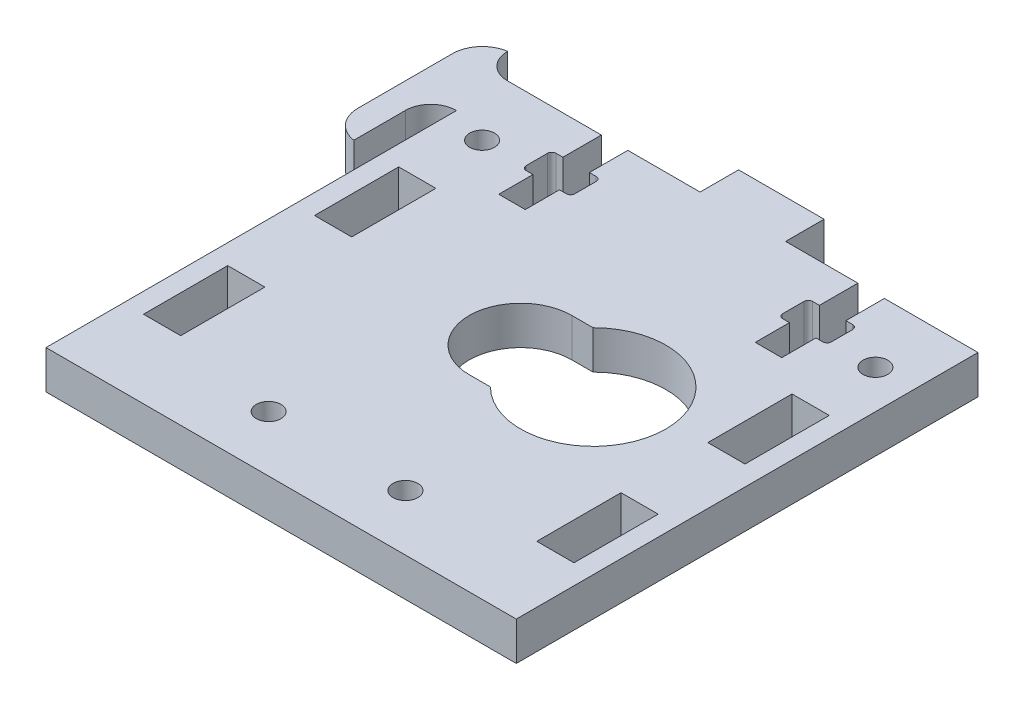
SolidWorks part; units mm, degrees
ref_plane "Front Plane" through (0, 0, 0) normal (0, 0, 1) x (1, 0, 0)
ref_plane "Top Plane" through (0, 0, 0) normal (0, 1, 0) x (1, 0, 0)
ref_plane "Right Plane" through (0, 0, 0) normal (1, 0, 0) x (0, 0, -1)
sketch "Sketch1" plane through (0, 0, 0) normal (0, 1, 0) x (1, 0, 0)
  line L1 (-27.5, 27) -> (27.5, 27)
  line L2 (-27.5, 27) -> (-27.5, -27)
  line L3 (-27.5, -27) -> (27.5, -27)
  line L4 (27.5, 27) -> (27.5, -27)
  line L5 (-27.5, 27) -> (27.5, -27) construction
  line L6 (-27.5, -27) -> (27.5, 27) construction
  point P0 (0, 0)
  dimension "D1" = 55
  dimension "D2" = 54
extrude "MainShape" add sketch "Sketch1" along normal blind 4.5
sketch "Sketch2" plane through (0, 4.5, 0) normal (0, 1, 0) x (1, 0, 0)
  line L0 (0, -27) -> (0, 27) construction
  line L1 (-27.5, -27) -> (27.5, -27) construction
  line L2 (27.5, 27) -> (-27.5, 27) construction
  line L4 (-5, 31.5) -> (5, 31.5)
  line L5 (-5, 31.5) -> (-5, 22.5)
  line L6 (-5, 22.5) -> (5, 22.5)
  line L7 (5, 31.5) -> (5, 22.5)
  line L8 (-5, 31.5) -> (5, 22.5) construction
  line L9 (-5, 22.5) -> (5, 31.5) construction
  dimension "D1" = 10
  dimension "D2" = 4.5
extrude "Tab1" add sketch "Sketch2" against normal through all
sketch "Sketch4" plane through (0, 4.5, 0) normal (0, 1, 0) x (1, 0, 0)
  line L0 (0, 31.5) -> (0, -27) construction
  line L1 (5, 31.5) -> (-5, 31.5) construction
  line L2 (-27.5, -27) -> (27.5, -27) construction
  line L3 (-15, 27) -> (-15, 15) construction
  line L4 (-5, 27) -> (-27.5, 27) construction
  line L5 (-13.45, 15) -> (-16.55, 15) construction
  line L6 (-16.55, 15) -> (-16.55, 27) construction
  line L7 (-13.45, 15) -> (-16.55, 15)
  line L8 (-16.55, 15) -> (-16.55, 19)
  line L9 (-16.55, 19) -> (-17.35, 19)
  line L10 (-17.85, 19.5) -> (-17.85, 22)
  line L11 (-17.35, 22.5) -> (-16.55, 22.5)
  line L12 (-16.55, 22.5) -> (-16.55, 27)
  line L13 (-16.55, 27) -> (-13.45, 27)
  line L14 (-13.45, 15) -> (-13.45, 27) construction
  line L15 (-13.45, 22.5) -> (-13.45, 27)
  line L16 (-12.65, 22.5) -> (-13.45, 22.5)
  line L17 (-12.15, 19.5) -> (-12.15, 22)
  line L18 (-13.45, 19) -> (-12.65, 19)
  line L19 (-13.45, 15) -> (-13.45, 19)
  line L20 (13.45, 15) -> (13.45, 27) construction
  line L21 (16.55, 15) -> (16.55, 27) construction
  line L22 (13.45, 15) -> (16.55, 15) construction
  line L23 (15, 27) -> (15, 15) construction
  line L24 (13.45, 15) -> (13.45, 19)
  line L25 (13.45, 19) -> (12.65, 19)
  line L26 (12.15, 19.5) -> (12.15, 22)
  line L27 (12.65, 22.5) -> (13.45, 22.5)
  line L28 (13.45, 22.5) -> (13.45, 27)
  line L29 (16.55, 27) -> (13.45, 27)
  line L30 (16.55, 22.5) -> (16.55, 27)
  line L31 (17.35, 22.5) -> (16.55, 22.5)
  line L32 (17.85, 19.5) -> (17.85, 22)
  line L33 (16.55, 19) -> (17.35, 19)
  line L34 (16.55, 15) -> (16.55, 19)
  line L35 (13.45, 15) -> (16.55, 15)
  arc A0 (-17.35, 19) -> (-17.85, 19.5) centre (-17.35, 19.5) cw
  arc A1 (-12.15, 19.5) -> (-12.65, 19) centre (-12.65, 19.5) cw
  arc A2 (-12.65, 22.5) -> (-12.15, 22) centre (-12.65, 22) cw
  arc A3 (-17.85, 22) -> (-17.35, 22.5) centre (-17.35, 22) cw
  arc A4 (17.85, 22) -> (17.35, 22.5) centre (17.35, 22) ccw
  arc A5 (12.65, 22.5) -> (12.15, 22) centre (12.65, 22) ccw
  arc A6 (12.15, 19.5) -> (12.65, 19) centre (12.65, 19.5) ccw
  arc A7 (17.35, 19) -> (17.85, 19.5) centre (17.35, 19.5) ccw
  point P24 (-17.85, 19)
  point P27 (-12.15, 19)
  point P30 (-12.15, 22.5)
  point P33 (-17.85, 22.5)
  point P56 (17.85, 22.5)
  point P57 (12.15, 22.5)
  point P58 (12.15, 19)
  point P59 (17.85, 19)
  dimension "D7" = 0.5
  dimension "D1" = 12
  dimension "D2" = 1.55
  dimension "D3" = 3.5
  dimension "D4" = 2.85
  dimension "D5" = 8
  dimension "D6" = 15
extrude "Cut-Extrude2" cut sketch "Sketch4" against normal through all
sketch "Sketch5" plane through (0, 4.5, 0) normal (0, 1, 0) x (1, 0, 0)
  line L0 (0, -27) -> (0, 31.5) construction
  line L1 (-27.5, -27) -> (27.5, -27) construction
  line L2 (5, 31.5) -> (-5, 31.5) construction
  line L3 (23, 27) -> (23, -27) construction
  line L4 (27.5, 27) -> (16.55, 27) construction
  line L5 (-23, 27) -> (-23, -27) construction
  line L6 (20.825, 11.925) -> (25.175, 11.925)
  line L7 (20.825, 11.925) -> (20.825, 2.075)
  line L8 (20.825, 2.075) -> (25.175, 2.075)
  line L9 (25.175, 11.925) -> (25.175, 2.075)
  line L10 (20.825, 11.925) -> (25.175, 2.075) construction
  line L11 (20.825, 2.075) -> (25.175, 11.925) construction
  line L12 (-20.825, 2.075) -> (-25.175, 11.925) construction
  line L13 (-20.825, 11.925) -> (-25.175, 2.075) construction
  line L14 (-25.175, 11.925) -> (-25.175, 2.075)
  line L15 (-20.825, 2.075) -> (-25.175, 2.075)
  line L16 (-20.825, 11.925) -> (-20.825, 2.075)
  line L17 (-20.825, 11.925) -> (-25.175, 11.925)
  line L18 (-27.5, -3) -> (27.5, -3) construction
  line L19 (-27.5, 27) -> (-27.5, -27) construction
  line L20 (27.5, -27) -> (27.5, 27) construction
  line L21 (-20.825, -17.925) -> (-25.175, -8.075) construction
  line L22 (-20.825, -8.075) -> (-25.175, -17.925) construction
  line L23 (20.825, -8.075) -> (25.175, -17.925) construction
  line L24 (20.825, -17.925) -> (25.175, -8.075) construction
  line L25 (-20.825, -17.925) -> (-25.175, -17.925)
  line L26 (-20.825, -17.925) -> (-20.825, -8.075)
  line L27 (-20.825, -8.075) -> (-25.175, -8.075)
  line L28 (-25.175, -17.925) -> (-25.175, -8.075)
  line L29 (25.175, -17.925) -> (25.175, -8.075)
  line L30 (20.825, -8.075) -> (25.175, -8.075)
  line L31 (20.825, -17.925) -> (20.825, -8.075)
  line L32 (20.825, -17.925) -> (25.175, -17.925)
  line L33 (-20.825, 11.925) -> (-25.175, 2.075) construction
  point P10 (23, 7)
  point P21 (-23, 7)
  point P36 (-23, -13)
  point P37 (23, -13)
  dimension "D1" = 23
  dimension "D2" = 9.85
  dimension "D3" = 4.35
  dimension "D4" = 20
  dimension "D5" = 20
extrude "Cut-Extrude3" cut sketch "Sketch5" against normal through all
sketch "Sketch6" plane through (0, 4.5, 0) normal (0, 1, 0) x (1, 0, 0)
  line L0 (0, -27) -> (0, 27) construction
  line L1 (5, 31.5) -> (-5, 31.5) construction
  line L3 (-27.5, 1) -> (27.5, 1) construction
  line L4 (-27.5, 27) -> (-27.5, -27) construction
  line L5 (27.5, -27) -> (27.5, 27) construction
  line L6 (27.5, 27) -> (16.55, 27) construction
  line L7 (-27.5, -27) -> (27.5, -27) construction
  line L9 (-27.5, 27) -> (27.5, 27) construction
  circle A0 centre (0, 1) radius 12
  point P4 (0, 31.5)
  dimension "D1" = 24
  dimension "D2" = 26
extrude "Cut-Extrude4" cut sketch "Sketch6" against normal through all
sketch "Sketch7" plane through (0, 4.5, 0) normal (0, 1, 0) x (1, 0, 0)
  line L0 (0, 1) -> (0, -27) construction
  line L3 (-27.5, -27) -> (27.5, -27) construction
  line L4 (8, -20.46) -> (-8, -20.46) construction
  circle A1 centre (-8, -20.46) radius 1.45
  circle A2 centre (8, -20.46) radius 1.45
  point P8 (0, -20.46)
  dimension "D1" = 2.9
  dimension "D3" = 21.46
extrude "Cut-Extrude5" [suppressed] cut sketch "Sketch7" against normal through all
sketch "Sketch8" plane through (0, 4.5, 0) normal (0, 1, 0) x (1, 0, 0)
  line L0 (-12, 1) -> (12, 1) construction
  line L1 (0, 1) -> (0, -20.46) construction
  line L2 (8, -20.46) -> (-8, -20.46) construction
  line L3 (0, -11) -> (0, 13) construction
  circle A0 centre (-8, -20.46) radius 1.45
  circle A1 centre (0, 1) radius 12 construction
  circle A2 centre (8, -20.46) radius 1.45
  dimension "D3" = 2.9
  dimension "D1" = 90
  dimension "D4" = 21.46
extrude "Cut-Extrude6" cut sketch "Sketch8" against normal through all
sketch "Sketch9" plane through (0, 4.5, 0) normal (0, 1, 0) x (1, 0, 0)
  line L0 (0, -27) -> (0, 31.5) construction
  line L1 (-27.5, -27) -> (27.5, -27) construction
  line L2 (5, 31.5) -> (-5, 31.5) construction
  line L3 (16, -27) -> (16, -16) construction
  line L4 (14.45, -16) -> (17.55, -16) construction
  line L5 (17.55, -16) -> (17.55, -27) construction
  line L6 (17.55, -27) -> (17.55, -22.5)
  line L7 (17.55, -22.5) -> (18.35, -22.5)
  line L8 (18.85, -22) -> (18.85, -19.5)
  line L9 (18.35, -19) -> (17.55, -19)
  line L10 (17.55, -19) -> (17.55, -16)
  line L11 (17.55, -16) -> (14.45, -16)
  line L12 (17.55, -27) -> (14.45, -27)
  line L13 (14.45, -16) -> (14.45, -27) construction
  line L14 (14.45, -19) -> (14.45, -16)
  line L15 (13.65, -19) -> (14.45, -19)
  line L16 (13.15, -22) -> (13.15, -19.5)
  line L17 (14.45, -22.5) -> (13.65, -22.5)
  line L18 (14.45, -27) -> (14.45, -22.5)
  line L19 (-14.45, -16) -> (-14.45, -27) construction
  line L20 (-17.55, -16) -> (-17.55, -27) construction
  line L21 (-14.45, -16) -> (-17.55, -16) construction
  line L22 (-16, -27) -> (-16, -16) construction
  line L23 (-14.45, -27) -> (-14.45, -22.5)
  line L24 (-14.45, -22.5) -> (-13.65, -22.5)
  line L25 (-13.15, -22) -> (-13.15, -19.5)
  line L26 (-13.65, -19) -> (-14.45, -19)
  line L27 (-14.45, -19) -> (-14.45, -16)
  line L28 (-17.55, -27) -> (-14.45, -27)
  line L29 (-17.55, -16) -> (-14.45, -16)
  line L30 (-17.55, -19) -> (-17.55, -16)
  line L31 (-18.35, -19) -> (-17.55, -19)
  line L32 (-18.85, -22) -> (-18.85, -19.5)
  line L33 (-17.55, -22.5) -> (-18.35, -22.5)
  line L34 (-17.55, -27) -> (-17.55, -22.5)
  arc A0 (18.35, -22.5) -> (18.85, -22) centre (18.35, -22) ccw
  arc A1 (18.85, -19.5) -> (18.35, -19) centre (18.35, -19.5) ccw
  arc A2 (13.15, -19.5) -> (13.65, -19) centre (13.65, -19.5) cw
  arc A3 (13.65, -22.5) -> (13.15, -22) centre (13.65, -22) cw
  arc A4 (-13.65, -22.5) -> (-13.15, -22) centre (-13.65, -22) ccw
  arc A5 (-13.15, -19.5) -> (-13.65, -19) centre (-13.65, -19.5) ccw
  arc A6 (-18.85, -19.5) -> (-18.35, -19) centre (-18.35, -19.5) cw
  arc A7 (-18.35, -22.5) -> (-18.85, -22) centre (-18.35, -22) cw
  point P16 (18.85, -22.5)
  point P19 (18.85, -19)
  point P30 (13.15, -19)
  point P31 (13.15, -22.5)
  point P54 (-13.15, -22.5)
  point P55 (-13.15, -19)
  point P56 (-18.85, -19)
  point P57 (-18.85, -22.5)
  dimension "D7" = 0.5
  dimension "D2" = 1.55
  dimension "D1" = 11
  dimension "D3" = 8
  dimension "D4" = 3.5
  dimension "D5" = 2.85
  dimension "D6" = 16
extrude "Cut-Extrude7" [suppressed] cut sketch "Sketch9" against normal through all
sketch "Sketch10" [suppressed] plane through (0, 0, 27) normal (0, 0, 1) x (1, 0, 0)
  line L0 (-27.5, 2.25) -> (27.5, 2.25) construction
  line L1 (-27.5, 4.5) -> (-27.5, 0) construction
  line L2 (27.5, 4.5) -> (27.5, 0) construction
  line L3 (-16, 4.5) -> (-16, 0) construction
  line L4 (-14.25, 4.5) -> (-17.75, 4.5) construction
  line L5 (16, 4.5) -> (16, 0) construction
  line L6 (17.75, 4.5) -> (14.25, 4.5) construction
  line L7 (17.75, 0) -> (14.25, 0) construction
  line L8 (-14.25, 0) -> (-17.75, 0) construction
  circle A0 centre (-16, 2.25) radius 1.6
  circle A1 centre (16, 2.25) radius 1.6
  dimension "D1" = 3.2
  dimension "D2" = 3.2
sketch "Sketch11" plane through (0, 4.5, 0) normal (0, 1, 0) x (1, 0, 0)
  line L0 (-20.825, 7) -> (-25.175, 7) construction
  line L1 (-20.825, 2.075) -> (-20.825, 11.925) construction
  line L2 (-25.175, 11.925) -> (-25.175, 2.075) construction
  line L3 (-23, 7) -> (-23, 27) construction
  line L4 (-16.55, 27) -> (-27.5, 27) construction
  line L5 (0, 31.5) -> (0, 0) construction
  line L6 (5, 31.5) -> (-5, 31.5) construction
  line L7 (23, 7) -> (23, 27) construction
  line L8 (20.825, 7) -> (25.175, 7) construction
  line L9 (-23, 7) -> (-23, 27) construction
  circle A0 centre (-23, 19.5) radius 1.45
  circle A1 centre (23, 19.5) radius 1.45
  dimension "D1" = 2.9
  dimension "D2" = 7.5
extrude "Cut-Extrude8" cut sketch "Sketch11" against normal through all
sketch "Sketch12" [suppressed] plane through (0, 4.5, 0) normal (0, 1, 0) x (1, 0, 0)
  line L0 (-27.5, -7) -> (-34, -17)
  line L1 (-27.5, 27) -> (-27.5, -27) construction
  line L2 (-34, -17) -> (-34, -27)
  line L3 (-34, -27) -> (-27.5, -27)
  line L4 (-27.5, -27) -> (-27.5, -7)
  line L5 (-27.5, -27) -> (27.5, -27) construction
  line L6 (0, -27) -> (0, 31.5) construction
  line L7 (5, 31.5) -> (-5, 31.5) construction
  line L8 (27.5, -27) -> (27.5, -7)
  line L9 (34, -27) -> (27.5, -27)
  line L10 (34, -17) -> (34, -27)
  line L11 (27.5, -7) -> (34, -17)
  point P4 (0, -27)
  dimension "D1" = 34
  dimension "D2" = 10
  dimension "D3" = 20
extrude "Boss-Extrude1" [suppressed] add sketch "Sketch12" against normal through all
sketch "Sketch14" [suppressed] plane through (0, 4.5, 0) normal (0, 1, 0) x (1, 0, 0)
  line L0 (-34, -27) -> (34, -27) construction
  line L2 (-34, -27) -> (34, -27) construction
  line L3 (0, -27) -> (0, 31.5) construction
  line L4 (5, 31.5) -> (-5, 31.5) construction
  line L6 (26.25, -16.5) -> (26.25, -27) construction
  line L8 (-28, -27) -> (-28, -16.5) construction
  line L9 (-26.25, -16.5) -> (-29.75, -16.5) construction
  line L10 (-29.75, -16.5) -> (-29.75, -27) construction
  line L11 (-26.25, -27) -> (-29.75, -27)
  line L12 (-29.75, -27) -> (-29.75, -23.2)
  line L13 (-29.75, -23.2) -> (-30.75, -23.2)
  line L14 (-31, -22.95) -> (-31, -19.25)
  line L15 (-30.75, -19) -> (-29.75, -19)
  line L16 (-29.75, -19) -> (-29.75, -16.5)
  line L17 (-29.75, -16.5) -> (-26.25, -16.5)
  line L18 (-26.25, -16.5) -> (-26.25, -27) construction
  line L19 (-26.25, -19) -> (-26.25, -16.5)
  line L20 (-25.25, -19) -> (-26.25, -19)
  line L21 (-25, -22.95) -> (-25, -19.25)
  line L22 (-26.25, -23.2) -> (-25.25, -23.2)
  line L23 (-26.25, -27) -> (-26.25, -23.2)
  line L24 (29.75, -16.5) -> (29.75, -27) construction
  line L25 (26.25, -16.5) -> (29.75, -16.5) construction
  line L26 (28, -27) -> (28, -16.5) construction
  line L27 (26.25, -27) -> (26.25, -23.2)
  line L28 (26.25, -23.2) -> (25.25, -23.2)
  line L29 (25, -22.95) -> (25, -19.25)
  line L30 (25.25, -19) -> (26.25, -19)
  line L31 (26.25, -19) -> (26.25, -16.5)
  line L32 (29.75, -16.5) -> (26.25, -16.5)
  line L33 (29.75, -19) -> (29.75, -16.5)
  line L34 (30.75, -19) -> (29.75, -19)
  line L35 (31, -22.95) -> (31, -19.25)
  line L36 (29.75, -23.2) -> (30.75, -23.2)
  line L37 (29.75, -27) -> (29.75, -23.2)
  line L38 (26.25, -27) -> (29.75, -27)
  line L39 (-26.25, -16.5) -> (-26.25, -27) construction
  arc A0 (-30.75, -23.2) -> (-31, -22.95) centre (-30.75, -22.95) cw
  arc A1 (-31, -19.25) -> (-30.75, -19) centre (-30.75, -19.25) cw
  arc A2 (-25, -19.25) -> (-25.25, -19) centre (-25.25, -19.25) ccw
  arc A3 (-25.25, -23.2) -> (-25, -22.95) centre (-25.25, -22.95) ccw
  arc A4 (25.25, -23.2) -> (25, -22.95) centre (25.25, -22.95) cw
  arc A5 (25, -19.25) -> (25.25, -19) centre (25.25, -19.25) cw
  arc A6 (31, -19.25) -> (30.75, -19) centre (30.75, -19.25) ccw
  arc A7 (30.75, -23.2) -> (31, -22.95) centre (30.75, -22.95) ccw
  point P2 (0, -27)
  dimension "D10" = 0.5
  dimension "D4" = 1.55
  dimension "D6" = 11
  dimension "D2" = 28
  dimension "D3" = 2.85
  dimension "D5" = 3.5
  dimension "D7" = 8
extrude "Cut-Extrude9" [suppressed] cut sketch "Sketch14" against normal through all
sketch "Sketch15" plane through (0, 4.5, 0) normal (0, 1, 0) x (1, 0, 0)
  circle A0 centre (0, 1) radius 12
  circle A1 centre (0, 1) radius 6
  circle A2 centre (0, 1) radius 12 construction
  dimension "D1" = 12
extrude "Boss-Extrude2" add sketch "Sketch15" against normal through all
sketch "Sketch16" plane through (0, 4.5, 0) normal (0, 1, 0) x (1, 0, 0)
  line L0 (0, 1) -> (27.5, 1) construction
  line L1 (27.5, -27) -> (27.5, 27) construction
  line L2 (0, 7) -> (2.4792, 7)
  line L3 (0, -5) -> (2.4792, -5)
  line L4 (0, 7) -> (0, -5)
  arc A0 (2.4792, -5) -> (2.4792, 7) centre (8.5, 1) ccw
  circle A1 centre (0, 1) radius 6 construction
  dimension "D1" = 17
  dimension "D2" = 8.5
extrude "Cut-Extrude10" cut sketch "Sketch16" against normal through all
sketch "Sketch17" plane through (0, 4.5, 0) normal (0, 1, 0) x (1, 0, 0)
  line L0 (-27.5, 22) -> (-27.5, 18) construction
  line L1 (-27.5, 27) -> (-27.5, -27) construction
  line L2 (-27.5, 25.5) -> (-27.5, 23.5)
  line L3 (-29, 22) -> (-29, 18)
  line L4 (-27.5, 22) -> (-27.5, 18) construction
  line L5 (-27.5, 16.5) -> (-27.5, 14.5)
  line L6 (-31, 22) -> (-31, 18)
  line L7 (-27.5, 25.5) -> (-27.5, 14.5) construction
  arc A0 (-27.5, 23.5) -> (-29, 22) centre (-27.5, 22) ccw
  arc A1 (-29, 18) -> (-27.5, 16.5) centre (-27.5, 18) ccw
  arc A2 (-27.5, 25.5) -> (-31, 22) centre (-27.5, 22) ccw
  arc A3 (-31, 18) -> (-27.5, 14.5) centre (-27.5, 18) ccw
  point P10 (-27.5, 20)
  dimension "D1" = 1.5
  dimension "D2" = 1.5
  dimension "D3" = 2
  dimension "D4" = 4
  dimension "D5" = 20
  dimension "D7" = 2
extrude "CableTieSlot" [suppressed] add sketch "Sketch17" against normal through all
sketch "Sketch18" plane through (0, 4.5, 0) normal (0, 1, 0) x (1, 0, 0)
  line L0 (-27.5, 27) -> (-27.55, 27)
  line L1 (-33.5, 30) -> (-33.5, 12)
  line L2 (-33.5, 12) -> (-30.5, 12)
  line L3 (-30.5, 12) -> (-30.5, 18.05)
  line L4 (-27.55, 21) -> (-27.5, 21)
  line L5 (-27.5, 27) -> (-27.5, -27) construction
  line L6 (-27.5, 21) -> (-27.5, 27)
  line L7 (-16.55, 27) -> (-27.5, 27) construction
  line L8 (-33.5, 30) -> (-30.5, 30)
  line L9 (-30.5, 30) -> (-30.5, 29.95)
  arc A0 (-27.55, 27) -> (-30.5, 29.95) centre (-27.55, 29.95) cw
  arc A1 (-30.5, 18.05) -> (-27.55, 21) centre (-27.55, 18.05) cw
  point P17 (-30.5, 27)
  dimension "D1" = 2.95
  dimension "D2" = 2.95
  dimension "D3" = 6
  dimension "D4" = 3
  dimension "D5" = 15
  dimension "D6" = 3
  dimension "D7" = 3
extrude "Boss-Extrude3" add sketch "Sketch18" against normal through all
fillet "Fillet1" radius 3.5 2 edges at (-33.5, 2.25, -30) (-33.5, 2.25, -12)
equation "\"X-ROD-SPACING\"=45"
equation "\"Y-ROD-SPACING\"=75"
equation "\"Z-ROD-SPACING\"=17.5"
equation "\"Y-BED-OFFSET\"=2"
equation "\"Y-BED-ROD-INSET\"=3.5"
equation "\"Y-BED-SCREW-SPACING\"=209"
equation "\"Y-BED-SCREW-CUTOUT-SLOT-HEIGHT\"=2.5"
equation "\"T-SLOT-NUT-FILLET-RADIUS\"=0.5"
equation "\"T-SLOT-SCREW-SHAFT-RADIUS\"=1.55"
equation "\"T-SLOT-SCREW-SHAFT-CUTOUT-LENGTH\"=11"
equation "\"T-SLOT-NUT-DEPTH\"=3.5"
equation "\"T-SLOT-NUT-WIDTH\"=2.85"
equation "\"T-SLOT-NUT-END-DISTANCE\"=8"
equation "\"ACRYLIC-THICKNESS\"=10"
equation "\"ACRYLIC-THICKNESS2\"=4.5"
equation "\"ACRYLIC-TAB-CUTOUT-SIZE\"=\"ACRYLIC-THICKNESS\"+\"ACRYLIC-TAB-TOLERANCE\"*2"
equation "\"ACRYLIC-TAB-WIDTH\"=\"ACRYLIC-THICKNESS\""
equation "\"ACRYLIC-M3-HOLE\"=2.9"
equation "\"SMOOTHROD-CAP-SCREW-DISTANCE\"=20"
equation "\"FRAME-WIDTH-INNER\"=370"
equation "\"NEMA17-HOLE-SPACING\"=31"
equation "\"NEMA17-CENTRAL-CUTOUT\"=22.5"
equation "\"Z-BRACKET-REACH\"=57"
equation "\"Z-ROD-INSET\"=13.5"
equation "\"TOP-BRACKET-SPACING\"=40"
equation "\"SMOOTHROD-X-LENGTH\"=350"
equation "\"SMOOTHROD-Y-LENGTH\"=350"
equation "\"SMOOTHROD-Z-LENGTH\"=350"
equation "\"SMOOTHROD-TIGHTENING-HEADROOM\"=.25"
equation "\"LEADSCREW-Z-LENGTH\"=300"
equation "\"SCREW-LENGTH-FRAME\"=\"ACRYLIC-THICKNESS\" + 10"
equation "\"SCREW-LENGTH-MOTOR\"=\"ACRYLIC-THICKNESS\" + 5"
equation "\"SCREW-LENGTH-EXTRUDER\"=28"
equation "\"SCREW-HEAD-RADIUS\"=6"
equation "\"PRINTED-X-SMOOTHROD-DIAMETER\"=8.8"
equation "\"PRINTED-X-SMOOTHROD-CUTOUT\"=10"
equation "\"PRINTED-X-BASE-HEIGHT\"=10"
equation "\"PRINTED-LM8UU-CUTOUT-SIZE\"=15.5"
equation "\"PRINTED-LM8UU-CUTOUT-LENGTH\"=24.5"
equation "\"PRINTED-X-IDLER-HEIGHT\"=16"
equation "\"PSU-MOUNTING-WIDTH\"=95"
equation "\"PSU-MOUNTING-HEIGHT\"=177"
equation "\"Y-BELT-TO-ROD-DISTANCE\"=20"
equation "\"SPOOL-HOLDER-ROD-SPACING\"=150"
equation "\"ACRYLIC-X-CARRIAGE-WIDTH\"=55"
equation "\"ACRYLIC-X-CARRIAGE-HEIGHT\"=75"
equation "\"ACRYLIC-X-CARRIAGE-SCREW-SPACING-X\"=15"
equation "\"ACRYLIC-X-CARRIAGE-SCREW-SPACING-Y\"=33"
equation "\"ACRYLIC-X-CARRIAGE-CENTER-TAB-SPACING\"=14"
equation "\"D1@Sketch1\"=\"ACRYLIC-X-CARRIAGE-WIDTH\""
equation "\"D1@MainShape\" = \"ACRYLIC-THICKNESS2\""
equation "\"D1@Sketch2\"=\"ACRYLIC-TAB-WIDTH\""
equation "\"D2@Sketch2\"=\"ACRYLIC-THICKNESS2\""
equation "\"D1@Sketch4\"=\"T-SLOT-SCREW-SHAFT-CUTOUT-LENGTH\"+1"
equation "\"D2@Sketch4\"=\"T-SLOT-SCREW-SHAFT-RADIUS\""
equation "\"D3@Sketch4\"=\"T-SLOT-NUT-DEPTH\""
equation "\"D4@Sketch4\"=\"T-SLOT-NUT-WIDTH\""
equation "\"D5@Sketch4\"=\"T-SLOT-NUT-END-DISTANCE\""
equation "\"D6@Sketch4\"=\"ACRYLIC-X-CARRIAGE-SCREW-SPACING-X\""
equation "\"D7@Sketch4\"=\"T-SLOT-NUT-FILLET-RADIUS\""
equation "\"ACRYLIC-X-CARRIAGE-EXTRUDER-SHELF-DEPTH\"=\"ACRYLIC-X-CARRIAGE-EXTRUDER-OFFSET\" + 28"
equation "\"D2@Sketch1\"=\"ACRYLIC-X-CARRIAGE-EXTRUDER-SHELF-DEPTH\""
equation "\"ACRYLIC-X-CARRIAGE-LM8UU-CUTOUT-WIDTH\"=24.25"
equation "\"ACRYLIC-X-CARRIAGE-EXTRUDER-BRACE-SPACING\"=23"
equation "\"ACRYLIC-X-CARRIAGE-EXTRUDER-BRACE-TAB-OFFSET\"=20"
equation "\"ACRYLIC-X-CARRIAGE-EXTRUDER-BRACE-HEIGHT\"=35"
equation "\"ACRYLIC-X-CARRIAGE-EXTRUDER-BRACE-SCREW-SPACING\"=22"
equation "\"D1@Sketch5\"=\"ACRYLIC-X-CARRIAGE-EXTRUDER-BRACE-SPACING\""
equation "\"D2@Sketch5\"=\"ACRYLIC-TAB-WIDTH\"-\"KERF\"*2"
equation "\"D3@Sketch5\"=\"ACRYLIC-THICKNESS2\"-\"KERF\"*2"
equation "\"D4@Sketch5\"=\"ACRYLIC-X-CARRIAGE-EXTRUDER-BRACE-TAB-OFFSET\""
equation "\"D1@Sketch7\"=\"ACRYLIC-M3-HOLE\""
equation "\"D3@Sketch8\"=\"ACRYLIC-M3-HOLE\""
equation "\"ACRYLIC-X-CARRIAGE-EXTRUDER-ANGLE\"=90"
equation "\"D1@Sketch8\"=\"ACRYLIC-X-CARRIAGE-EXTRUDER-ANGLE\""
equation "\"ACRYLIC-X-CARRIAGE-EXTRUDER-OFFSET\"=26"
equation "\"D2@Sketch6\"=\"ACRYLIC-X-CARRIAGE-EXTRUDER-OFFSET\""
equation "\"D1@Sketch9\"=\"T-SLOT-SCREW-SHAFT-CUTOUT-LENGTH\""
equation "\"D2@Sketch9\"=\"T-SLOT-SCREW-SHAFT-RADIUS\""
equation "\"D3@Sketch9\"=\"T-SLOT-NUT-END-DISTANCE\""
equation "\"D4@Sketch9\"=\"T-SLOT-NUT-DEPTH\""
equation "\"D5@Sketch9\"=\"T-SLOT-NUT-WIDTH\""
equation "\"D7@Sketch9\"=\"T-SLOT-NUT-FILLET-RADIUS\""
equation "\"ACRYLIC-TAB-TOLERANCE\"=-.05"
equation "\"D1@Sketch11\"=\"ACRYLIC-M3-HOLE\""
equation "\"D6@Sketch14\"=\"T-SLOT-SCREW-SHAFT-CUTOUT-LENGTH\""
equation "\"D3@Sketch14\"=\"T-SLOT-NUT-WIDTH\""
equation "\"D5@Sketch14\"=\"T-SLOT-NUT-DEPTH\""
equation "\"D4@Sketch14\"=\"T-SLOT-SCREW-SHAFT-RADIUS\""
equation "\"D10@Sketch14\"=\"T-SLOT-NUT-FILLET-RADIUS\""
equation "\"D7@Sketch14\"=\"T-SLOT-NUT-END-DISTANCE\""
equation "\"KERF\"=0.075"
equation "\"PRINTED-M3-HOLE\"=3.5"
equation "\"PRINTED-M3-NUT-AF\"=6.25"
equation "\"ACRYLIC-X-CARRIAGE-LM8UU-CUTOUT-HEIGHT\"=11.0"
equation "\"ACRYLIC-X-CARRIAGE-DUAL-WIDTH-MULTIPLIER\"=1.65"
equation "\"ACRYLIC-X-CARRIAGE-DUAL-HOTEND-SPACING\"=42"
equation "\"ACRYLIC-X-CARRIAGE-DUAL-WIDTH\"=75"
equation "\"ACRYLIC-X-CARRIAGE-DUAL-FAN-OFFSET\"=52"
equation "\"ACRYLIC-X-CARRIAGE-DUAL-FAN-HEIGHT\"=20"
equation "\"ACRYLIC-X-CARRIAGE-DUAL-HOTEND-SEPARATION\"=36"
equation "\"ACRYLIC-X-CARRIAGE-DUAL-MOUNT-PLATE-DEPTH\"=75"
equation "\"ACRYLIC-X-CARRIAGE-DUAL-MOUNT-BRACE-WIDTH\"=33"
equation "\"ACRYLIC-X-CARRIAGE-DUAL-MOUNT-SCREW-WIDTH\"=40"
equation "\"BLOWER-FAN-WIDTH\"=15"
